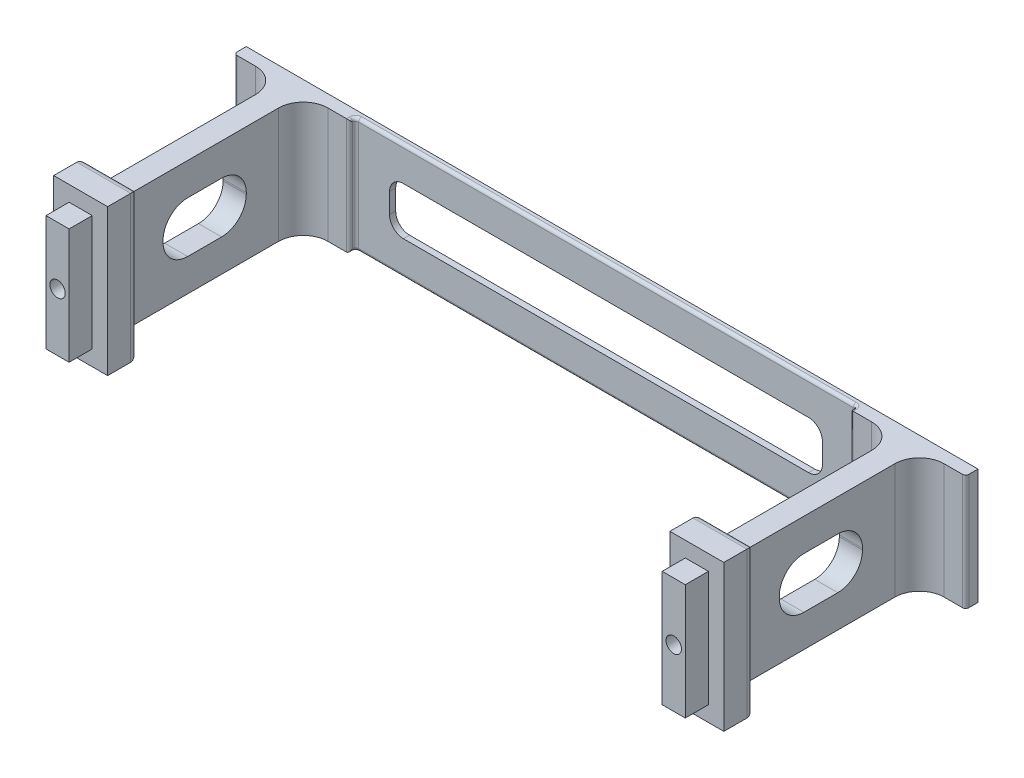
SolidWorks part; units mm, degrees
material "PLA"
ref_plane "Front Plane" through (0, 0, 0) normal (0, 0, 1) x (1, 0, 0)
ref_plane "Top Plane" through (0, 0, 0) normal (0, 1, 0) x (1, 0, 0)
ref_plane "Right Plane" through (0, 0, 0) normal (1, 0, 0) x (0, 0, -1)
sketch "Sketch1" plane through (0, 0, 0) normal (0, 0, 1) x (1, 0, 0)
  line L0 (-29.6428, 21.4337) -> (-29.6428, 6.4337)
  line L1 (-37.1428, 21.4337) -> (42.8572, 21.4337)
  line L2 (-37.1428, 21.4337) -> (-37.1428, 6.4337) construction
  line L3 (-37.1428, 6.4337) -> (42.8572, 6.4337)
  line L4 (42.8572, 21.4337) -> (42.8572, 6.4337) construction
  line L5 (35.3572, 21.4337) -> (35.3572, 6.4337)
  line L6 (-37.1428, 21.4337) -> (-44.6428, 21.4337)
  line L7 (-44.6428, 21.4337) -> (-44.6428, 6.4337)
  line L8 (-44.6428, 6.4337) -> (-37.1428, 6.4337)
  line L9 (42.8572, 21.4337) -> (50.3572, 21.4337)
  line L10 (50.3572, 21.4337) -> (50.3572, 6.4337)
  line L11 (50.3572, 6.4337) -> (42.8572, 6.4337)
  line L12 (-38.6428, 21.4337) -> (-38.6428, 6.4337)
  line L13 (-35.6428, 21.4337) -> (-35.6428, 6.4337)
  line L14 (41.3572, 21.4337) -> (41.3572, 6.4337)
  line L15 (44.3572, 21.4337) -> (44.3572, 6.4337)
  dimension "D1" = 80
  dimension "D2" = 15
  dimension "D3" = 7.5
  dimension "D4" = 7.5
  dimension "D5" = 7.5
  dimension "D6" = 7.5
  dimension "D7" = 1.5
  dimension "D8" = 1.5
  dimension "D9" = 1.5
  dimension "D10" = 1.5
extrude "Boss-Extrude1" add sketch "Sketch1" along normal blind 0.8 contours L5 L1 L0 L3 region at (2.8572, 13.9337, 0)
extrude "Boss-Extrude2" add sketch "Sketch1<3>" along normal blind 1.6 contours L1 L13 L3 L0 | L12 L6 L7 L8 | L14 L1 L5 L3 | L9 L15 L11 L10 region at (-32.6428, 13.9337, 0) region at (38.3572, 13.9337, 0) region at (-41.6428, 13.9337, 0) region at (47.3572, 13.9337, 0)
sketch "Sketch1<3>" plane through (0, 0, 0) normal (0, 0, 1) x (1, 0, 0) same geometry as "Sketch1"
extrude "Boss-Extrude3" add sketch "Sketch1<4>" along normal blind 29 contours L13 L1 L6 L12 L8 L3 | L15 L9 L1 L14 L3 L11 region at (-37.1428, 13.9337, 0) region at (42.8572, 13.9337, 0)
sketch "Sketch1<4>" plane through (0, 0, 0) normal (0, 0, 1) x (1, 0, 0) same geometry as "Sketch1"
ref_plane "Plane1" through (0, 0, 29) normal (0, 0, 1) x (1, 0, 0)
sketch "Sketch2" plane through (0, 0, 29) normal (0, 0, 1) x (1, 0, 0)
  line L36 (-40.6428, 4.4337) -> (-33.6428, 4.4337)
  line L37 (-33.6428, 23.4337) -> (-40.6428, 23.4337)
  line L38 (-33.6428, 4.4337) -> (-33.6428, 23.4337)
  line L39 (-40.6428, 23.4337) -> (-40.6428, 4.4337)
  line L40 (-40.6428, 4.4337) -> (-33.6428, 4.4337)
  line L41 (-33.6428, 23.4337) -> (-40.6428, 23.4337)
  line L42 (-33.6428, 4.4337) -> (-33.6428, 23.4337)
  line L43 (-40.6428, 23.4337) -> (-40.6428, 4.4337)
  line L44 (-38.6428, 21.4337) -> (-38.6428, 6.4337) construction
  line L45 (-35.6428, 21.4337) -> (-35.6428, 6.4337) construction
  line L46 (-38.6428, 21.4337) -> (-35.6428, 21.4337) construction
  line L47 (-38.6428, 6.4337) -> (-35.6428, 6.4337) construction
  line L48 (39.3572, 4.4337) -> (46.3572, 4.4337)
  line L49 (46.3572, 23.4337) -> (39.3572, 23.4337)
  line L50 (46.3572, 4.4337) -> (46.3572, 23.4337)
  line L51 (39.3572, 23.4337) -> (39.3572, 4.4337)
  line L52 (39.3572, 4.4337) -> (46.3572, 4.4337)
  line L53 (46.3572, 23.4337) -> (39.3572, 23.4337)
  line L54 (46.3572, 4.4337) -> (46.3572, 23.4337)
  line L55 (39.3572, 23.4337) -> (39.3572, 4.4337)
  line L56 (41.3572, 21.4337) -> (44.3572, 21.4337) construction
  line L57 (41.3572, 21.4337) -> (41.3572, 6.4337) construction
  line L58 (44.3572, 21.4337) -> (44.3572, 6.4337) construction
  line L59 (41.3572, 6.4337) -> (44.3572, 6.4337) construction
  line L60 (-38.6428, 21.4337) -> (-38.6428, 6.4337)
  line L61 (-35.6428, 21.4337) -> (-35.6428, 6.4337)
  line L62 (-38.6428, 21.4337) -> (-35.6428, 21.4337)
  line L63 (-38.6428, 6.4337) -> (-35.6428, 6.4337)
  line L64 (41.3572, 21.4337) -> (44.3572, 21.4337)
  line L65 (41.3572, 21.4337) -> (41.3572, 6.4337)
  line L66 (44.3572, 21.4337) -> (44.3572, 6.4337)
  line L67 (41.3572, 6.4337) -> (44.3572, 6.4337)
  dimension "D1" = 2
  dimension "D2" = 2
extrude "Boss-Extrude4" add sketch "Sketch2" against normal blind 4
extrude "Boss-Extrude5" add sketch "Sketch2<2>" along normal blind 3 contours L60 L63 L61 L62 | L66 L67 L65 L64 region at (-37.1428, 13.9337, 29)
sketch "Sketch2<2>" plane through (0, 0, 29) normal (0, 0, 1) x (1, 0, 0) same geometry as "Sketch2"
sketch "Sketch3" plane through (0, 0, 32) normal (0, 0, 1) x (1, 0, 0)
  line L0 (-38.6428, 21.4337) -> (-35.6428, 21.4337) construction
  line L1 (-38.6428, 21.4337) -> (-38.6428, 6.4337) construction
  line L2 (44.3572, 21.4337) -> (44.3572, 6.4337) construction
  circle A0 centre (-37.1428, 13.9337) radius 1
  circle A1 centre (42.8572, 13.9337) radius 1
  dimension "D1" = 2
  dimension "D4" = 2
  dimension "D2" = 7.5
  dimension "D3" = 1.5
  dimension "D5" = 1.5
extrude "Cut-Extrude1" cut sketch "Sketch3" against normal blind 4.6
fillet "Fillet1" radius 3.2 4 edges
fillet "Fillet2" radius 0.4 12 edges at (50.3572, 13.9337, 1.6) (35.3572, 13.9337, 1.6) (-29.6428, 13.9337, 1.6) (-44.6428, 13.9337, 1.6)
fillet "Fillet3" radius 1 16 edges at (-37.1428, 23.4337, 25) (-40.6428, 13.9337, 25) (-33.6428, 13.9337, 25) (-37.1428, 4.4337, 25) (42.8572, 23.4337, 25) (39.3572, 13.9337, 25) (42.8572, 4.4337, 25) (46.3572, 13.9337, 25) (42.8572, 6.4337, 25) (41.3572, 13.9337, 25) (42.8572, 21.4337, 25) (44.3572, 13.9337, 25) (-37.1428, 21.4337, 25) (-35.6428, 13.9337, 25) (-37.1428, 6.4337, 25) (-38.6428, 13.9337, 25)
sketch "Sketch4" plane through (0, 0, 0.8) normal (0, 0, 1) x (1, 0, 0)
  line L8 (30.9572, 10.8337) -> (30.9572, 17.0337)
  line L9 (-25.2428, 10.8337) -> (30.9572, 10.8337)
  line L10 (-25.2428, 17.0337) -> (-25.2428, 10.8337)
  line L11 (30.9572, 17.0337) -> (-25.2428, 17.0337)
  line L12 (30.9572, 10.8337) -> (30.9572, 17.0337)
  line L13 (-25.2428, 10.8337) -> (30.9572, 10.8337)
  line L14 (-25.2428, 17.0337) -> (-25.2428, 10.8337)
  line L15 (30.9572, 17.0337) -> (-25.2428, 17.0337)
  dimension "D1" = 4
extrude "Cut-Extrude2" cut sketch "Sketch4" against normal through all
fillet "Fillet4" radius 1.8 4 edges at (-25.2428, 10.8337, 0.4) (30.9572, 10.8337, 0.4) (30.9572, 17.0337, 0.4) (-25.2428, 17.0337, 0.4)
sketch "Sketch5" plane through (44.3572, 0, 0) normal (1, 0, 0) x (0, 0, -1)
  line L8 (-9, 17.2337) -> (-19.8, 17.2337)
  line L9 (-9, 10.6337) -> (-9, 17.2337)
  line L10 (-19.8, 10.6337) -> (-9, 10.6337)
  line L11 (-19.8, 17.2337) -> (-19.8, 10.6337)
  line L12 (-9, 17.2337) -> (-19.8, 17.2337)
  line L13 (-9, 10.6337) -> (-9, 17.2337)
  line L14 (-19.8, 10.6337) -> (-9, 10.6337)
  line L15 (-19.8, 17.2337) -> (-19.8, 10.6337)
  dimension "D1" = 4.2
extrude "Cut-Extrude3" cut sketch "Sketch5" against normal through all
fillet "Fillet5" radius 3.2 8 edges at (-37.1428, 17.2337, 19.8) (-37.1428, 10.6337, 19.8) (-37.1428, 10.6337, 9) (-37.1428, 17.2337, 9) (42.8572, 17.2337, 9) (42.8572, 10.6337, 9) (42.8572, 10.6337, 19.8) (42.8572, 17.2337, 19.8)
equation "\"D4@Sketch1\"=\"D3@Sketch1\""
equation "\"D5@Sketch1\"=\"D3@Sketch1\""
equation "\"D6@Sketch1\"=\"D3@Sketch1\""
